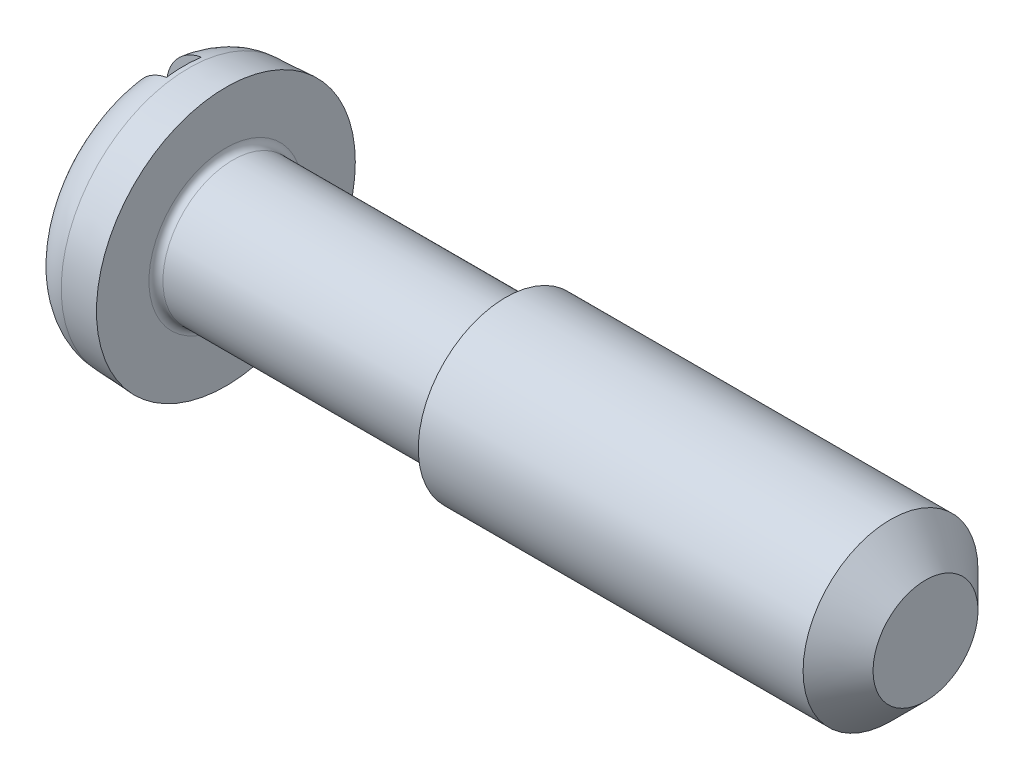
SolidWorks part; units mm, degrees
ref_plane "Front" through (0, 0, 0) normal (0, 0, 1) x (1, 0, 0)
ref_plane "Top" through (0, 0, 0) normal (0, 1, 0) x (1, 0, 0)
ref_plane "Right" through (0, 0, 0) normal (1, 0, 0) x (0, 0, -1)
ref_plane "Plane1" through (1.1, 0, 0) normal (1, 0, 0) x (0, 0, -1)
sketch "Sketch1" plane through (1.1, 0, 0) normal (1, 0, 0) x (0, 0, -1)
  circle A0 centre (0, 0) radius 1.85
  dimension "dk" = 3.7
extrude "BaseHead" add sketch "Sketch1" against normal blind 1.1 draft 3
sketch "Sketch2" plane through (1.1, 0.2245, -0.1603) normal (1, 0, 0) x (0, 0, -1)
  circle A0 centre (-0.1603, -0.2245) radius 1
  circle A1 centre (-0.1603, -0.2245) radius 1.85 construction
  dimension "d1" = 2
extrude "BaseBody" add sketch "Sketch2" along normal blind 10
fillet "HeadFillet" radius 0.6 1 edges at (0, 0, -1.7924)
sketch "Sketch3" plane through (-0.85, 0, 0.85) normal (0, 1, 0) x (0, 0, -1)
  line L1 (0.6, -0.85) -> (1.1, -0.85)
  line L2 (0.6, -0.85) -> (0.6, -1.35)
  line L3 (0.6, -1.35) -> (1.1, -1.35)
  line L4 (1.1, -0.85) -> (1.1, -1.35)
  dimension "t" = 0.5
  dimension "m" = 0.25
extrude "Slot" cut sketch "Sketch3" against normal through all and the other way through all
sketch "Sketch4" plane through (11.1, -0.1571, -0.7581) normal (1, 0, 0) x (0, 0, -1)
  circle A0 centre (-0.7581, 0.1571) radius 1.25
  circle A1 centre (-0.7581, 0.1571) radius 1 construction
extrude "BaseEnd" add sketch "Sketch4" against normal blind 6
cosmetic thread "ThreadCosmetic1" [suppressed] parameters "THD_MINOR"=1.75
chamfer "Chamfer1" distance 0.5 angle 45 1 edges at (11.1, 0, -1.25)
fillet "Fillet1" radius 0.1 2 edges at (1.1, 0, -1) (5.1, 0, -1)
sketch "Sketch5" plane through (0, 0, 0) normal (0, 0, 1) x (1, 0, 0)
  line L0 (5.1, 0.9252) -> (5.2875, 1.25)
  line L1 (5.2875, 1.25) -> (5.2875, 1.625)
  line L2 (5.2875, 1.625) -> (4.9125, 1.625)
  line L3 (4.9125, 1.625) -> (4.9125, 1.25)
  line L4 (4.9125, 1.25) -> (5.1, 0.9252)
  line L6 (5.1, 1.25) -> (5.1, -1.25) construction
  line L7 (0, 0) -> (6.6036, 0) construction
  line L8 (0, 1.1971) -> (0, -1.1971) construction
  dimension "D1" = 2.5
  dimension "D2" = 0.375
revolve "Cut-Revolve10" [suppressed] cut sketch "Sketch5" angle 360 about L7
pattern_linear "LPattern10" [suppressed] count 13 spacing 0.45 along (1, 0, 0) of bodies 105
equation "\"m@Sketch3\" = \"n@Sketch3\" / 2"
equation "\"D1@Plane1\"=\"k@BaseHead\""
equation "\"D1@Sketch5\" = \"d@Sketch4\""
equation "\"D2@Sketch5\" =  ( \"d@Sketch4\" - \"THD_MINOR@ThreadCosmetic1\" )  / 2"
equation "\"D3@LPattern10\" = \"D2@Sketch5\" * 1.2"
equation "\"D1@LPattern10\" = \"b@BaseEnd\" / \"D3@LPattern10\""
